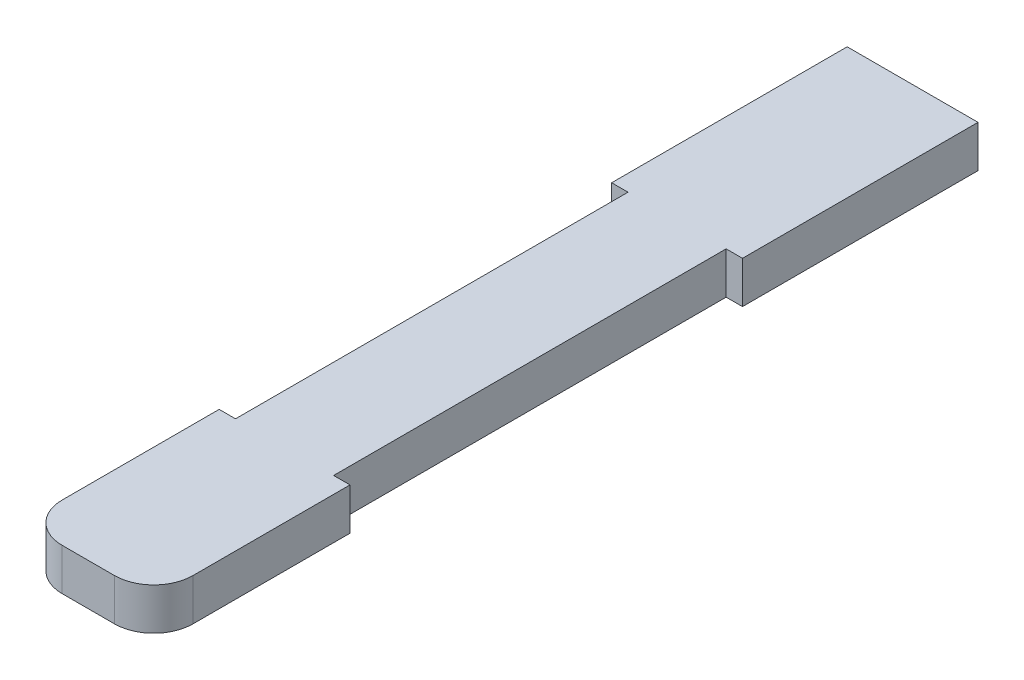
SolidWorks part; units mm, degrees
material "K110"
ref_plane "Front Plane" through (0, 0, 0) normal (0, 0, 1) x (1, 0, 0)
ref_plane "Top Plane" through (0, 0, 0) normal (0, 1, 0) x (1, 0, 0)
ref_plane "Right Plane" through (0, 0, 0) normal (1, 0, 0) x (0, 0, -1)
sketch "Sketch1" plane through (0, 0, 0) normal (0, 1, 0) x (1, 0, 0)
  line L1 (-5, -31.5) -> (5, -31.5)
  line L2 (-5, -31.5) -> (-5, 31.5)
  line L3 (-5, 31.5) -> (5, 31.5)
  line L4 (5, -31.5) -> (5, 31.5)
  line L5 (-5, -31.5) -> (5, 31.5) construction
  line L6 (-5, 31.5) -> (5, -31.5) construction
  point P0 (0, 0)
  dimension "D1" = 63
  dimension "D2" = 10
extrude "Boss-Extrude1" add sketch "Sketch1" against normal blind 3.2
fillet "Fillet1" radius 3 2 edges at (-5, -1.6, 31.5) (5, -1.6, 31.5)
sketch "Sketch2" plane through (0, 0, 0) normal (0, 1, 0) x (1, 0, 0)
  line L7 (-5, 31.5) -> (-5, -28.5) construction
  line L8 (-5, -16.5) -> (-3.75, -16.5)
  line L9 (-5, -16.5) -> (-5, 13.5)
  line L10 (-5, 13.5) -> (-3.75, 13.5)
  line L11 (-3.75, -16.5) -> (-3.75, 13.5)
  line L12 (5, -28.5) -> (5, 31.5) construction
  line L13 (5, -16.5) -> (3.75, -16.5)
  line L14 (5, -16.5) -> (5, 13.5)
  line L15 (5, 13.5) -> (3.75, 13.5)
  line L16 (3.75, -16.5) -> (3.75, 13.5)
  line L18 (-2, -31.5) -> (2, -31.5) construction
  dimension "D1" = 7.5
  dimension "D3" = 15
  dimension "D4" = 30
extrude "Cut-Extrude1" cut sketch "Sketch2" against normal up to next
